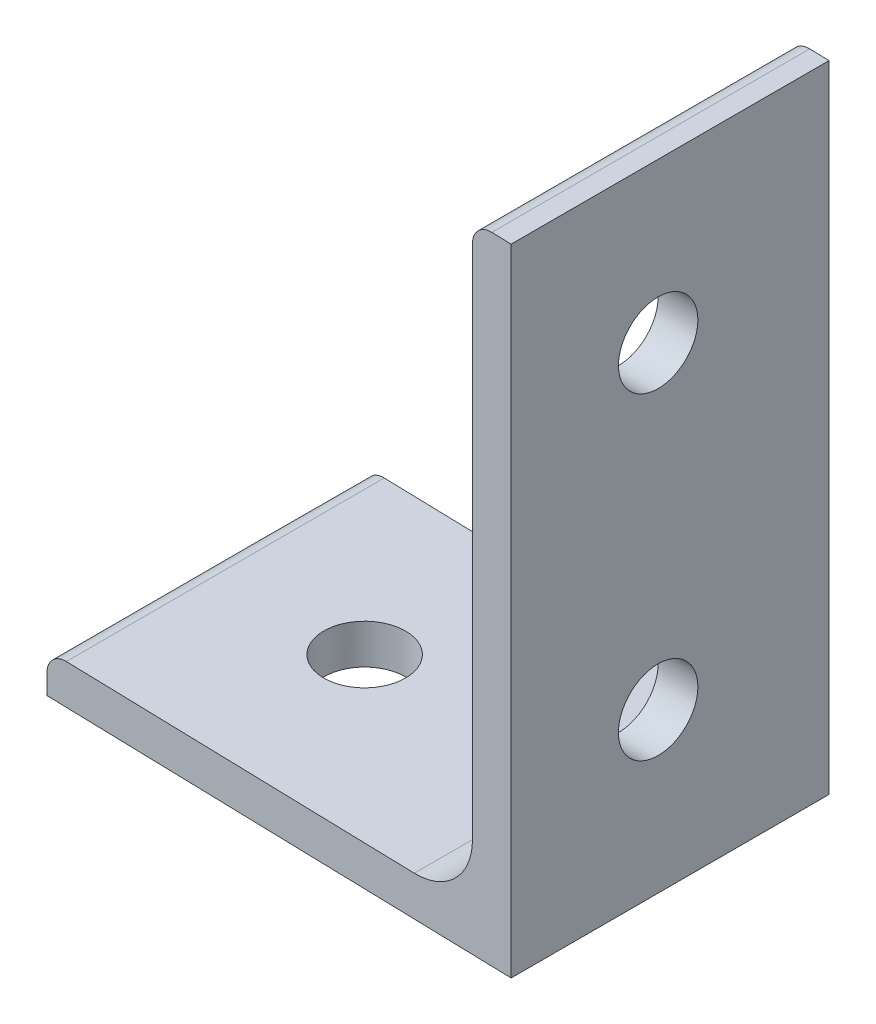
SolidWorks part; units mm, degrees
ref_plane "Front Plane" through (0, 0, 0) normal (0, 0, 1) x (1, 0, 0)
ref_plane "Top Plane" through (0, 0, 0) normal (0, 1, 0) x (1, 0, 0)
ref_plane "Right Plane" through (0, 0, 0) normal (1, 0, 0) x (0, 0, -1)
sketch "Sketch0" plane through (0, 0, 0) normal (0, 0, 1) x (1, 0, 0)
  line L0 (-19.05, -25.4) -> (19.05, -25.4)
  line L1 (19.05, -25.4) -> (19.05, 25.4)
  line L2 (19.05, 0) -> (0, 0) construction
  line L3 (0, 0) -> (0, -25.4) construction
  line L4 (15.875, -17.4498) -> (15.875, 25.4) construction
  line L5 (11.0998, -22.225) -> (-19.05, -22.225) construction
  arc A0 (15.875, -17.4498) -> (11.0998, -22.225) centre (11.0998, -17.4498) cw
  point P3 (14.4764, -20.8264)
  dimension "Inside Corner Radius" = 4.7752
  dimension "Outside Height" = 50.8
  dimension "Inside Height" = 47.625
  dimension "Inside Width" = 34.925
  dimension "Wall Thickness" = 3.175
  dimension "D1" = 3.175
  dimension "Outside Width" = 38.1
sketch "Sketch1" plane through (0, 0, 0) normal (1, 0, 0) x (0, 0, -1)
  line L0 (15.875, 0) -> (-15.875, 0)
  point P4 (0, 0)
  dimension "Length" = 31.75
sketch "Sketch2" plane through (0, 0, 0) normal (0, 0, 1) x (1, 0, 0)
  line L0 (-19.05, -25.4) -> (19.05, -25.4)
  line L1 (19.05, -25.4) -> (19.05, 25.4)
  line L2 (19.05, 25.4) -> (15.875, 25.4) construction
  line L3 (15.875, 23.8125) -> (15.875, -17.4498)
  line L4 (11.0998, -22.225) -> (-17.4625, -22.225)
  line L5 (-19.05, -25.4) -> (-19.05, -22.225) construction
  line L6 (17.4625, 25.4) -> (19.05, 25.4)
  line L7 (-19.05, -23.8125) -> (-19.05, -25.4)
  line L8 (19.05, 0) -> (0, 0) construction
  line L9 (0, 0) -> (0, -25.4) construction
  arc A0 (15.875, 23.8125) -> (17.4625, 25.4) centre (17.4625, 23.8125) cw
  arc A1 (-19.05, -23.8125) -> (-17.4625, -22.225) centre (-17.4625, -23.8125) cw
  arc A2 (15.875, -17.4498) -> (11.0998, -22.225) centre (11.0998, -17.4498) cw
  dimension "Inside Radius" = 4.7752
  dimension "Height" = 50.8
  dimension "Width" = 38.1
  dimension "Thickness" = 3.175
extrude "Boss-Extrude1" add sketch "Sketch2" along normal mid plane 31.75
sketch "Break Locations" plane through (0, 0, 0) normal (1, 0, 0) x (0, 0, -1)
  line L0 (35.941, 0) -> (-35.941, 0)
  line L1 (-15.875, -25.4) -> (-15.875, 25.4) construction
  line L2 (15.875, -25.4) -> (15.875, 25.4) construction
  point P0 (27.305, 0)
  point P1 (-27.305, 0)
  point P10 (0, 0)
  point P11 (-35.941, 0)
  point P13 (35.941, 0)
  dimension "D1" = 43.18
  dimension "D2" = 43.18
  dimension "D3" = 51.816
sketch "Sketch3" plane through (0, -25.4, 0) normal (0, -1, 0) x (1, 0, 0)
  line L1 (19.05, 15.875) -> (19.05, -15.875) construction
  line L6 (19.05, 0) -> (5.5904, 0) construction
  line L7 (19.05, -10.4842) -> (19.05, 14.9245)
  line L8 (-18.3851, -11.4645) -> (19.05, -10.4842)
  line L9 (-19.05, 13.9268) -> (-18.3851, -11.4645)
  line L10 (-19.05, 13.9268) -> (19.05, 14.9245)
sketch "Sketch4" plane through (19.05, 0, 0) normal (1, 0, 0) x (0, 0, -1)
  line L0 (-15.875, -25.4) -> (-3.175, -25.4) construction
  line L1 (-15.875, -25.4) -> (15.875, -25.4) construction
  line L2 (-3.175, -25.4) -> (-3.175, -12.7) construction
  line L3 (-3.175, -12.7) -> (-3.175, 12.7) construction
  circle A0 centre (-3.175, 12.7) radius 3.175
  circle A1 centre (-3.175, -12.7) radius 3.175
  dimension "D1" = 12.7
  dimension "D2" = 12.7
  dimension "D3" = 25.4
extrude "Cut-Extrude1" cut sketch "Sketch4" against normal through all
extrude "Cut-Extrude2" cut sketch "Sketch3" against normal through all flip side to cut
hole_wizard "1/4 Clearance Hole1" positions "Sketch7" profile "Sketch8" hole size "1/4" standard "ANSI Inch" end condition through all
sketch "Sketch7" plane through (0, -25.4, 0) normal (0, -1, 0) x (-1, 0, 0)
  point P4 (6.0219, -1.5636)
sketch "Sketch8" plane through (-6.0219, -25.4, 1.5636) normal (1, 0, 0) x (0, 0, -1)
  line L0 (0, 0) -> (0, 50.8)
  line L1 (0, 50.8) -> (3.2639, 50.8)
  line L2 (3.2639, 50.8) -> (3.2639, 0)
  line L5 (3.2639, 0) -> (0, 0)
  line L11 (0, -6.35) -> (0, 107.95) construction
  dimension "Thru Hole Dia." = 6.5278
  dimension "Thru Hole Depth" = 50.8
equation "\"D1@Break Locations\" = .85 * \"Height@Sketch2\""
equation "\"D2@Break Locations\"=\"D1@Break Locations\""
equation "\"Thickness@Sketch2\"=\"wall thickness@sketch0\""
equation "\"Height@Sketch2\"=\"outside height@sketch0\""
equation "\"Width@Sketch2\"=\"outside width@sketch0\""
equation "\"Inside Radius@Sketch2\"=\"inside corner radius@sketch0\""
equation "\"Length@Boss-Extrude1\"=\"length@sketch1\""
equation "\"D3@Break Locations\"=\"D2@Break Locations\"*1.2"
equation "\"D1@Sketch0\"=\"Wall Thickness@Sketch0\""
